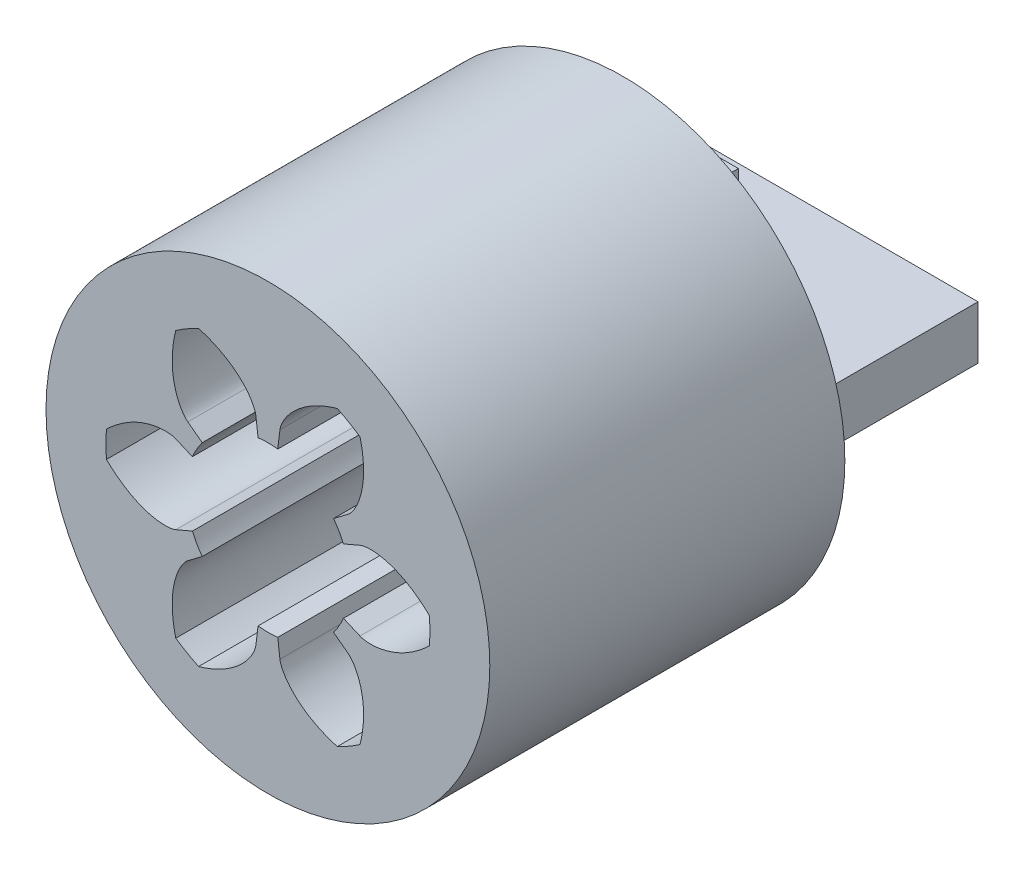
SolidWorks part; units mm, degrees
ref_plane "前视基准面" through (0, 0, 0) normal (0, 0, 1) x (1, 0, 0)
ref_plane "上视基准面" through (0, 0, 0) normal (0, 1, 0) x (1, 0, 0)
ref_plane "右视基准面" through (0, 0, 0) normal (1, 0, 0) x (0, 0, -1)
other "Configuration Table"
sketch "草图1" plane through (0, 0, 0) normal (0, 0, 1) x (1, 0, 0)
  line L0 (0, 0) -> (1.1087, 0.4592) construction
  line L1 (0, 0) -> (1.0372, 0.4425)
  line L2 (0, 0) -> (1.0372, -0.4425)
  line L3 (0, 0) -> (1.1087, -0.4592) construction
  line L4 (0, 0) -> (1.825, 0) construction
  line L5 (1.1087, 0.4592) -> (1.1087, -0.4592) construction
  circle A0 centre (0, 0) radius 0.925
  circle A1 centre (0, 0) radius 1.825
  circle A2 centre (0, 0) radius 1.1276 construction
  circle A3 centre (0, 0) radius 1.2 construction
  circle A4 centre (0, 0) radius 2.5
  spline S0 degree 4 poles (1.0372, 0.4425) (1.0451, 0.4458) (1.0679, 0.4536) (1.1133, 0.4615) (1.188, 0.4641) (1.2844, 0.4524) (1.4047, 0.4201) (1.5384, 0.3613) (1.6746, 0.2764) (1.8072, 0.1656) (1.9251, 0.0393) (2.0279, -0.0995) (2.12, -0.2556) (2.2132, -0.4598) (2.2925, -0.7157) (2.34, -1.0237) (2.3398, -1.3696) (2.2891, -1.712) (2.1939, -2.0438) (2.0552, -2.3616) (1.8823, -2.6586) (1.6708, -2.936) (1.4388, -3.184) (1.166, -3.413) (0.9461, -3.5671) (0.6842, -3.7168) (0.5292, -3.7919) (0.3505, -3.8722) (0.2497, -3.9065) (0.1672, -3.9381) (0.1423, -3.9451) (0.1243, -3.9513) knots 0 0 0 0 0 0.005604 0.015718 0.02996 0.048734 0.068727 0.096889 0.125051 0.153212 0.181374 0.209535 0.237696 0.271429 0.327752 0.384075 0.440398 0.496721 0.553044 0.609367 0.66569 0.722013 0.778336 0.834659 0.890982 0.909091 0.954545 0.977273 0.988636 1 1 1 1 1 construction
  spline S1 degree 4 poles (1.0372, 0.4425) (1.0451, 0.4458) (1.0679, 0.4536) (1.1133, 0.4615) (1.188, 0.4641) (1.2844, 0.4524) (1.4047, 0.4201) (1.5384, 0.3613) (1.6746, 0.2764) (1.8072, 0.1656) (1.9251, 0.0393) (2.0279, -0.0995) (2.12, -0.2556) (2.2132, -0.4598) (2.2925, -0.7157) (2.34, -1.0237) (2.3398, -1.3696) (2.2891, -1.712) (2.1939, -2.0438) (2.0552, -2.3616) (1.8823, -2.6586) (1.6708, -2.936) (1.4388, -3.184) (1.166, -3.413) (0.9461, -3.5671) (0.7517, -3.6782) (0.6596, -3.7265) (0.6372, -3.738) knots 0 0 0 0 0 0.005604 0.015718 0.02996 0.048734 0.068727 0.096889 0.125051 0.153212 0.181374 0.209535 0.237696 0.271429 0.327752 0.384075 0.440398 0.496721 0.553044 0.609367 0.66569 0.722013 0.778336 0.834659 0.890982 0.909091 0.909091 0.909091 0.909091 0.909091
  spline S2 degree 4 poles (1.0372, -0.4425) (1.0451, -0.4458) (1.0679, -0.4536) (1.1133, -0.4615) (1.188, -0.4641) (1.2844, -0.4524) (1.4047, -0.4201) (1.5384, -0.3613) (1.6746, -0.2764) (1.8072, -0.1656) (1.9251, -0.0393) (2.0279, 0.0995) (2.12, 0.2556) (2.2132, 0.4598) (2.2925, 0.7157) (2.34, 1.0237) (2.3398, 1.3696) (2.2891, 1.712) (2.1939, 2.0438) (2.0552, 2.3616) (1.8823, 2.6586) (1.6708, 2.936) (1.4388, 3.184) (1.166, 3.413) (0.9461, 3.5671) (0.6842, 3.7168) (0.5292, 3.7919) (0.3505, 3.8722) (0.2497, 3.9065) (0.1672, 3.9381) (0.1423, 3.9451) (0.1243, 3.9513) knots 0 0 0 0 0 0.005604 0.015718 0.02996 0.048734 0.068727 0.096889 0.125051 0.153212 0.181374 0.209535 0.237696 0.271429 0.327752 0.384075 0.440398 0.496721 0.553044 0.609367 0.66569 0.722013 0.778336 0.834659 0.890982 0.909091 0.954545 0.977273 0.988636 1 1 1 1 1 construction
  spline S3 degree 4 poles (1.0372, -0.4425) (1.0451, -0.4458) (1.0679, -0.4536) (1.1133, -0.4615) (1.188, -0.4641) (1.2844, -0.4524) (1.4047, -0.4201) (1.5384, -0.3613) (1.6746, -0.2764) (1.8072, -0.1656) (1.9251, -0.0393) (2.0279, 0.0995) (2.12, 0.2556) (2.2132, 0.4598) (2.2925, 0.7157) (2.34, 1.0237) (2.3398, 1.3696) (2.2891, 1.712) (2.1939, 2.0438) (2.0552, 2.3616) (1.8823, 2.6586) (1.6708, 2.936) (1.4388, 3.184) (1.166, 3.413) (0.9461, 3.5671) (0.7517, 3.6782) (0.6596, 3.7265) (0.6372, 3.738) knots 0 0 0 0 0 0.005604 0.015718 0.02996 0.048734 0.068727 0.096889 0.125051 0.153212 0.181374 0.209535 0.237696 0.271429 0.327752 0.384075 0.440398 0.496721 0.553044 0.609367 0.66569 0.722013 0.778336 0.834659 0.890982 0.909091 0.909091 0.909091 0.909091 0.909091
  point P16 (1.1087, 0)
  dimension "内啮合齿顶圆直径" = 1.85
  dimension "内啮合分度圆直径" = 2.4
  dimension "内啮合基圆直径" = 2.2553
  dimension "内啮合齿根圆直径" = 3.65
  dimension "外径" = 5
  dimension "渐开线镜像线夹角" = 22.5
extrude "凸台-拉伸1" add sketch "草图1" along normal blind 3 contours A4 | A0
extrude "切除-拉伸2" cut sketch "草图1<3>" along normal through all contours A0 S3 A1 S1 region at (1.3095, 0, 0)
sketch "草图1<3>" plane through (0, 0, 0) normal (0, 0, 1) x (1, 0, 0) same geometry as "草图1"
pattern_circular "阵列(圆周)1" count 6 over 360 about axis through (0, 0, 3) along (0, 0, 1) of "切除-拉伸2"
sketch "草图2" plane through (0, 0, 0) normal (0, 0, -1) x (-1, 0, 0)
  line L1 (-2, -0.3) -> (2, -0.3)
  line L2 (-2, -0.3) -> (-2, 0.3)
  line L3 (-2, 0.3) -> (2, 0.3)
  line L4 (2, -0.3) -> (2, 0.3)
  line L5 (-2, -0.3) -> (2, 0.3) construction
  line L6 (-2, 0.3) -> (2, -0.3) construction
  line L7 (0.3, -1.25) -> (-0.3, -1.25)
  line L8 (0.3, -1.25) -> (0.3, 1.25)
  line L9 (0.3, 1.25) -> (-0.3, 1.25)
  line L10 (-0.3, -1.25) -> (-0.3, 1.25)
  line L11 (0.3, -1.25) -> (-0.3, 1.25) construction
  line L12 (0.3, 1.25) -> (-0.3, -1.25) construction
  circle A0 centre (0, 0) radius 2.5
  circle A1 centre (0, 0) radius 2.5 construction
  dimension "D1" = 0.6
  dimension "D2" = 4
  dimension "D3" = 2.5
extrude "凸台-拉伸2" add sketch "草图2" along normal blind 1 contours A0
extrude "凸台-拉伸3" add sketch "草图2<3>" along normal blind 2 from surface contours L3 L4 L1 L2 starting at face at (-2.5, 0, -1)
sketch "草图2<3>" plane through (0, 0, 0) normal (0, 0, -1) x (-1, 0, 0) same geometry as "草图2"
extrude "凸台-拉伸4" add sketch "草图2<4>" along normal blind 1 from surface contours L10 L9 L8 L7 starting at face at (-2.5, 0, -1)
sketch "草图2<4>" plane through (0, 0, 0) normal (0, 0, -1) x (-1, 0, 0) same geometry as "草图2"
equation "\"m\"= 0.4'模数"
equation "\"z1\"= 6'外啮合齿轮数"
equation "\"a\"= 20度'压力角"
equation "\"z2\"= 6'内啮合齿轮数"
equation "\"hax\"= 1'齿顶高系数"
equation "\"cx\"= 0.25'顶隙系数"
equation "\"ha\"= \"hax\" * \"m\"'齿顶高"
equation "\"hf\"= ( \"hax\" + \"cx\" ) * \"m\"'齿根高"
equation "\"d1\"= \"m\" * \"z1\"'外啮合分度圆直径"
equation "\"da1\"= ( \"z1\" + 2 ) * \"m\"'外啮合齿顶圆直径"
equation "\"df1\"= \"d1\" - 2 * \"hf\"'外啮合齿根圆直径"
equation "\"db1\"= \"d1\" * cos ( \"a\" )'外啮合基圆直径"
equation "\"p\"= \"m\" * PI'齿距"
equation "\"d2\"= \"m\" * \"z2\"'内啮合分度圆直径"
equation "\"db2\"= \"d2\" * cos ( \"a\" )'内啮合基圆直径"
equation "\"da2\"= ( \"z2\" - 2 ) * \"m\"'内啮合齿顶圆直径"
equation "\"df2\"= \"d2\" + 2 * \"hf\"'内啮合齿根圆直径"
equation "\"内啮合齿顶圆直径@草图1\" = \"da2\" + 0.5 * \"hf\""
equation "\"内啮合齿根圆直径@草图1\"= \"df2\" + 0.5 * \"hf\""
equation "\"内啮合分度圆直径@草图1\"= \"d2\""
equation "\"内啮合基圆直径@草图1\"= \"db2\""
equation "\"渐开线镜像线夹角@草图1\"= 360度 / 4 / \"z2\" + 360度 / 4 / \"z2\" / 2"
equation "\"do\"= IIF ( \"edo\" >= ( \"df2\" + 1 ) , \"edo\" , ( \"df2\" + 1 ) )'外圈直径"
equation "\"h\"= 3'厚度"
equation "\"外径@草图1\"= \"do\""
equation "\"厚度@凸台-拉伸1\"= \"h\""
equation "\"内啮合齿轮数@阵列(圆周)1\"= \"z2\""
equation "\"edo\"= 5'期望的外圈直径"
